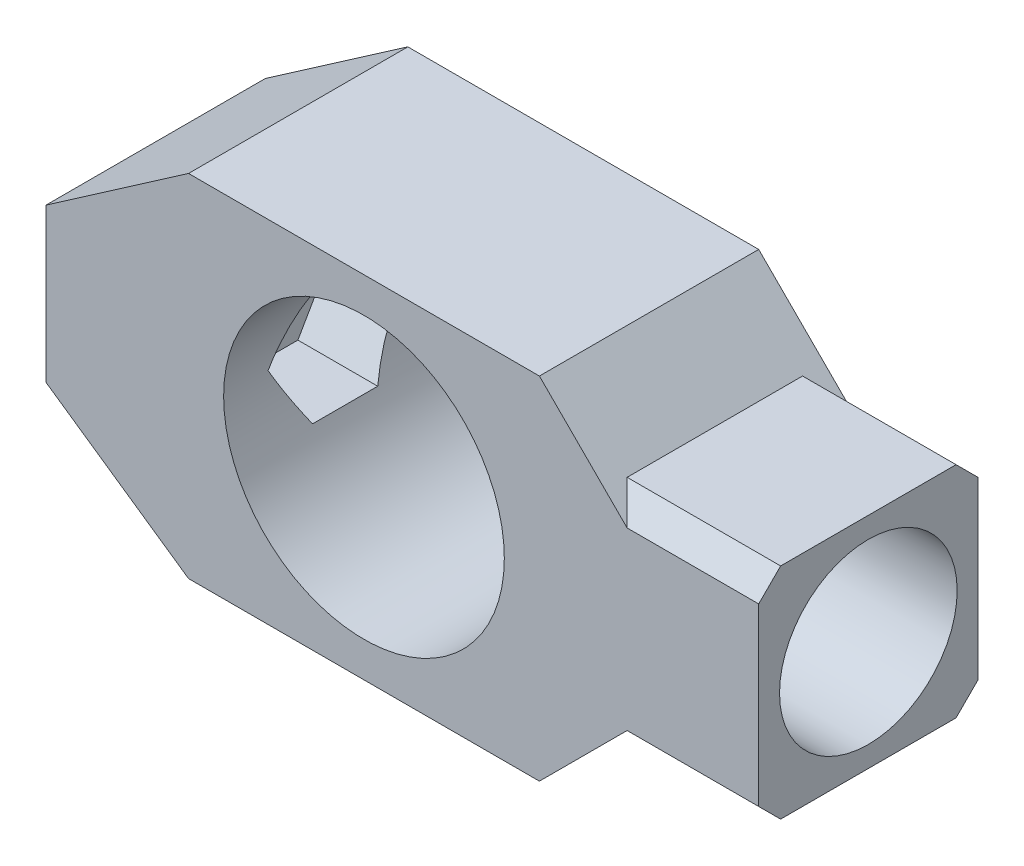
SolidWorks part; units mm, degrees
ref_plane "Plan de face" through (0, 0, 0) normal (0, 0, 1) x (1, 0, 0)
ref_plane "Plan de dessus" through (0, 0, 0) normal (0, 1, 0) x (1, 0, 0)
ref_plane "Plan de droite" through (0, 0, 0) normal (1, 0, 0) x (0, 0, -1)
sketch "Esquisse1" plane through (0, 0, 0) normal (0, 0, 1) x (1, 0, 0)
  line L1 (0, 0) -> (32, 0)
  line L2 (0, 0) -> (0, 32)
  line L3 (0, 32) -> (32, 32)
  line L4 (32, 0) -> (32, 32)
  dimension "D1" = 32
  dimension "D2" = 32
extrude "Boss.-Extru.1" add sketch "Esquisse1" along normal blind 20
sketch "Esquisse2" plane through (0, 0, 20) normal (0, 0, 1) x (1, 0, 0)
  line L0 (16, 0) -> (16, 32) construction
  line L1 (0, 0) -> (32, 0) construction
  line L2 (32, 32) -> (0, 32) construction
  circle A0 centre (16, 16) radius 12.8
  dimension "D1" = 25.6
extrude "Enlèv. mat.-Extru.1" cut sketch "Esquisse2" against normal through all both and the other way through all
sketch "Esquisse3" plane through (0, 0, 20) normal (0, 0, 1) x (1, 0, 0)
  line L0 (0, 0) -> (0, 32)
  line L1 (0, 32) -> (-13, 23)
  line L2 (-13, 23) -> (-13, 9)
  line L3 (-13, 9) -> (0, 0)
  line L4 (-13, 16) -> (0, 16) construction
  point P8 (-12, 8.6153)
  dimension "D1" = 13
  dimension "D2" = 14
extrude "Boss.-Extru.2" add sketch "Esquisse3" against normal up to vertex (20 mm away) up to point (0, 32, 0)
sketch "Esquisse4" plane through (-13, 0, 0) normal (-1, 0, 0) x (0, 0, 1)
  line L0 (0, 16) -> (20, 16) construction
  line L1 (0, 23) -> (0, 9) construction
  line L2 (20, 23) -> (20, 9) construction
  circle A0 centre (10, 16) radius 3.25
  dimension "D1" = 6.5
extrude "Enlèv. mat.-Extru.2" cut sketch "Esquisse4" against normal blind 10
sketch "Esquisse5" plane through (-3, 0, 0) normal (-1, 0, 0) x (0, 0, 1)
  line L0 (13.25, 16) -> (6.75, 16) construction
  line L1 (10, 12.75) -> (10, 16) construction
  line L2 (12.9734, 10.85) -> (15.9467, 16)
  line L3 (15.9467, 16) -> (12.9734, 21.15)
  line L4 (12.9734, 21.15) -> (7.0266, 21.15)
  line L5 (7.0266, 21.15) -> (4.0533, 16)
  line L6 (4.0533, 16) -> (7.0266, 10.85)
  line L7 (7.0266, 10.85) -> (12.9734, 10.85)
  line L8 (10, 16) -> (10, 19.25) construction
  circle A0 centre (10, 16) radius 3.25 construction
  circle A1 centre (10, 16) radius 3.25 construction
  circle A2 centre (10, 16) radius 5.15 construction
  dimension "D1" = 10.3
extrude "Enlèv. mat.-Extru.3" cut sketch "Esquisse5" against normal blind 20
sketch "Esquisse6" plane through (32, 0, 0) normal (1, 0, 0) x (0, 0, -1)
  line L0 (-20, 16) -> (0, 16) construction
  line L1 (-20, 0) -> (-20, 32) construction
  line L2 (0, 0) -> (0, 32) construction
  line L3 (0, 6) -> (0, 26)
  line L4 (0, 26) -> (-20, 26)
  line L5 (-20, 26) -> (-20, 6)
  line L6 (0, 6) -> (-20, 6)
  circle A0 centre (-10, 16) radius 8.1
  dimension "D1" = 16.2
  dimension "D2" = 20
extrude "Boss.-Extru.3" add sketch "Esquisse6" along normal blind 20
chamfer "Chanfrein1" distance 6 angle 45 2 edges at (32, 6, 10) (32, 26, 10)
chamfer "Chanfrein2" distance 2 angle 45 4 edges at (45, 6, 0) (45, 6, 20) (45, 26, 20) (45, 26, 0) tangent propagation no
sketch "Esquisse7" plane through (32, 0, 0) normal (1, 0, 0) x (0, 0, -1)
  circle A0 centre (-10, 16) radius 8.1
  circle A1 centre (-10, 16) radius 8.1 construction
extrude "Enlèv. mat.-Extru.4" cut sketch "Esquisse7" against normal blind 2
